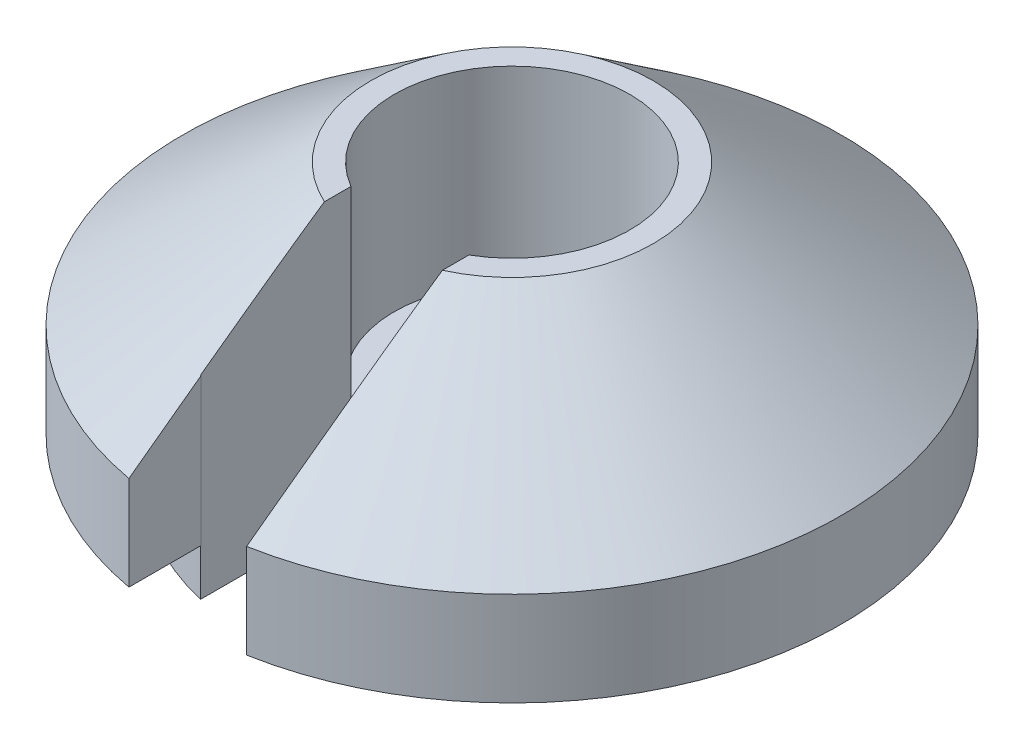
SolidWorks part; units mm, degrees
material "PBT General Purpose"
ref_plane "Front Plane" through (0, 0, 0) normal (0, 0, 1) x (1, 0, 0)
ref_plane "Top Plane" through (0, 0, 0) normal (0, 1, 0) x (1, 0, 0)
ref_plane "Right Plane" through (0, 0, 0) normal (1, 0, 0) x (0, 0, -1)
sketch "Sketch5" plane through (0, 0, 0) normal (0, 0, 1) x (1, 0, 0)
  line L0 (0, 0) -> (5.5, 0)
  line L1 (5.5, 0) -> (5.5, 1)
  line L2 (5.5, 1) -> (7, 1)
  line L3 (7, 1) -> (7, 3)
  line L4 (7, 3) -> (3, 6)
  line L5 (3, 6) -> (0, 6)
  line L6 (0, 6) -> (0, 0)
  dimension "D1" = 1
  dimension "D2" = 6
  dimension "D3" = 2
  dimension "D4" = 7
  dimension "D5" = 5.5
  dimension "D6" = 3
revolve "Revolve3" add sketch "Sketch5" angle 360 about L6
sketch "Sketch7" plane through (0, 6, 0) normal (0, 1, 0) x (1, 0, 0)
  circle A0 centre (0, 0) radius 2.5
  dimension "D1" = 5
extrude "Cut-Extrude2" cut sketch "Sketch7" against normal blind 4
sketch "Sketch8" plane through (0, 2, 0) normal (0, 1, 0) x (1, 0, 0)
  line L0 (-1.25, 0) -> (1.25, 0)
  line L2 (-1.25, 0) -> (-1.25, -7.259)
  line L3 (1.25, 0) -> (1.25, -7.259)
  line L4 (-1.25, -7.259) -> (1.25, -7.259)
  point P4 (0, 0)
  dimension "D1" = 2.5
extrude "Cut-Extrude3" cut sketch "Sketch8" against normal blind 4 and the other way blind 4
fillet "Fillet1" radius 1.5 2 edges at (1.25, 1, 0) (-1.25, 1, 0)
sketch "Sketch9" plane through (0, 0, 0) normal (0, -1, 0) x (-1, 0, 0)
  line L0 (1.25, -5.3561) -> (1.25, 0)
  line L1 (-1.25, -5.3561) -> (-1.25, 0)
  line L2 (-1.25, 0) -> (1.25, 0)
  line L3 (-1.25, -5.3561) -> (1.25, -5.3561)
extrude "Cut-Extrude4" cut sketch "Sketch9" against normal blind 10
fillet "Fillet2" radius 1.25 2 edges at (-1.25, 1, 0) (1.25, 1, 0)
sketch "Sketch10" plane through (0, 0, 0) normal (0, -1, 0) x (1, 0, 0)
  line L0 (1.25, 5.3561) -> (1.25, 0)
  line L1 (1.25, 5.3561) -> (-1.2532, 5.3561)
  line L2 (1.25, 0) -> (-1.2532, 0)
  line L3 (-1.2532, 5.3561) -> (-1.2532, 0)
  line L4 (1.25, 1.25) -> (1.25, 5.3561) construction
  arc A0 (-1.25, 5.3561) -> (1.25, 5.3561) centre (0, 0) ccw construction
extrude "Cut-Extrude5" cut sketch "Sketch10" against normal blind 10
sketch "Sketch11" plane through (0, 0, 0) normal (0, -1, 0) x (-1, 0, 0)
  line L0 (-1.25, -5.3561) -> (-1.25, 0.6453)
  line L1 (-1.25, -5.3561) -> (1.2532, -5.3561)
  line L2 (-1.25, 0.6453) -> (1.2532, 0.6453)
  line L3 (1.2532, -5.3561) -> (1.2532, 0.6453)
extrude "Cut-Extrude6" cut sketch "Sketch11" against normal blind 10
fillet "Fillet4" radius 1.25 2 edges at (1.25, 1, -0.6453) (-1.2532, 1, -0.6453)
sketch "Sketch12" plane through (0, 0, 0) normal (0, -1, 0) x (1, 0, 0)
  line L0 (1.25, 5.3561) -> (1.25, -0.3939)
  line L1 (1.25, 5.3561) -> (-1.2648, 5.3561)
  line L2 (1.25, -0.3939) -> (-1.2648, -0.3939)
  line L3 (-1.2648, 5.3561) -> (-1.2648, -0.3939)
  dimension "D1" = 5.75
extrude "Cut-Extrude9" cut sketch "Sketch12" against normal blind 10
sketch "Sketch14" plane through (0, 0, 0) normal (0, -1, 0) x (-1, 0, 0)
  line L0 (1.2648, 0.3939) -> (-1.25, 0.3939) construction
  circle A0 centre (0.0074, 0.3939) radius 1.249
  dimension "D1" = 2.4981
extrude "Cut-Extrude10" cut sketch "Sketch14" against normal blind 10
